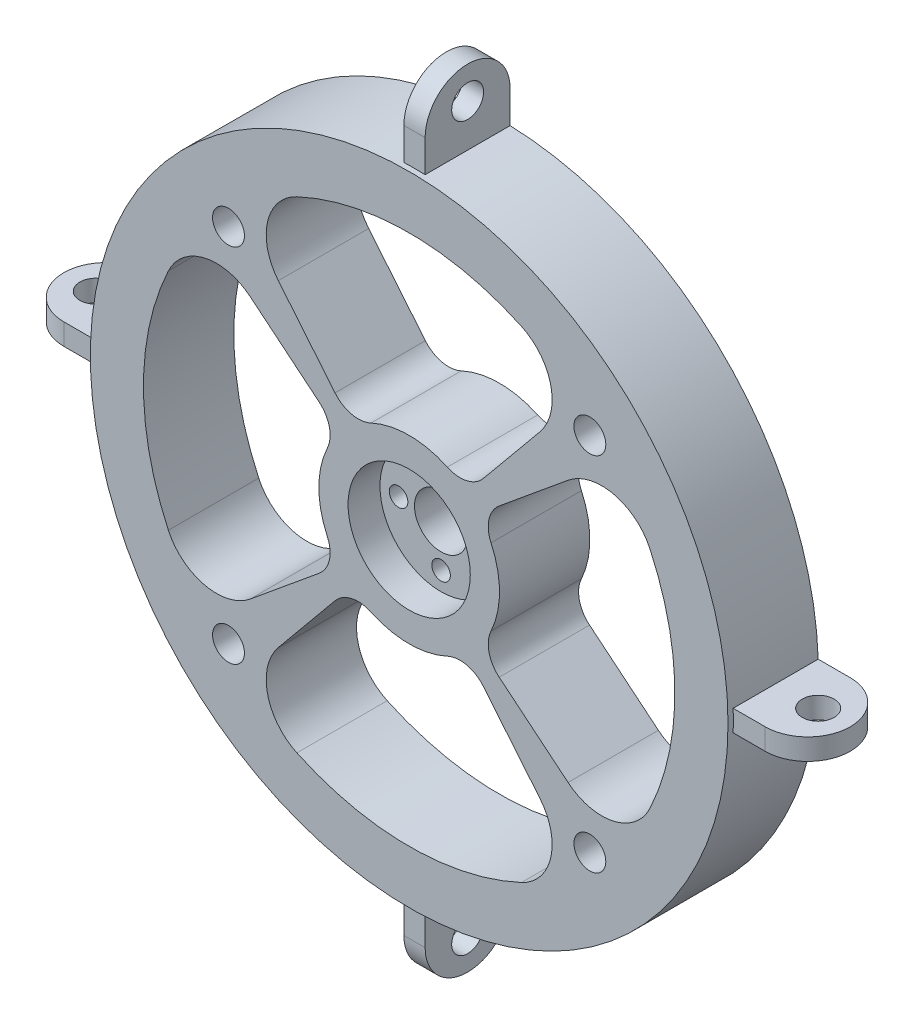
SolidWorks part; units mm, degrees
material "ABS"
ref_plane "前视基准面" through (0, 0, 0) normal (0, 0, 1) x (1, 0, 0)
ref_plane "上视基准面" through (0, 0, 0) normal (0, 1, 0) x (1, 0, 0)
ref_plane "右视基准面" through (0, 0, 0) normal (1, 0, 0) x (0, 0, -1)
sketch "草图1" plane through (0, 0, 0) normal (0, 0, 1) x (1, 0, 0)
  circle A0 centre (0, 0) radius 60
  dimension "D1" = 120
extrude "凸台-拉伸1" add sketch "草图1" along normal blind 17
sketch "草图2" plane through (0, 0, 17) normal (0, 0, 1) x (1, 0, 0)
  line L0 (0, 30) -> (0, 0) construction
  line L1 (0, 0) -> (0, -30) construction
  line L2 (-30, 0) -> (0, 0) construction
  line L3 (0, 0) -> (30, 0) construction
  circle A4 centre (-34, 34) radius 3
  circle A5 centre (34, 34) radius 3
  circle A6 centre (34, -34) radius 3
  circle A7 centre (-34, -34) radius 3
  dimension "D1" = 6
  dimension "D2" = 6
  dimension "D7" = 6
  dimension "D8" = 6
  dimension "D3" = 30
  dimension "D4" = 30
  dimension "D5" = 30
  dimension "D6" = 30
  dimension "D9" = 68
  dimension "D10" = 68
extrude "切除-拉伸1" cut sketch "草图2" against normal through all
sketch "草图3" plane through (0, 0, 0) normal (1, 0, 0) x (0, 0, -1)
  line L0 (0, 58) -> (-16, 58)
  line L1 (-16, 58) -> (-16, 66)
  line L2 (0, 66) -> (0, 58)
  line L3 (0, 0) -> (-35.6052, 0) construction
  arc A0 (-16, 66) -> (0, 66) centre (-8, 66) cw
  dimension "D3" = 8
  dimension "D1" = 58
  dimension "D2" = 8
  dimension "D4" = 0
extrude "凸台-拉伸2" add sketch "草图3" along normal blind 2 and the other way blind 2
sketch "草图4" plane through (2, 0, 0) normal (1, 0, 0) x (0, 0, -1)
  line L0 (-16, 59.9667) -> (0, 59.9667) construction
  line L1 (0, 59.9667) -> (0, 66) construction
  circle A0 centre (-8, 67.9667) radius 3
  dimension "D1" = 6
  dimension "D2" = 8
  dimension "D3" = 8
extrude "切除-拉伸7" cut sketch "草图4" against normal through all
sketch "草图5" plane through (0, 0, 0) normal (0, 0, -1) x (-1, 0, 0)
  circle A0 centre (0, 0) radius 5
  dimension "D1" = 10
extrude "切除-拉伸3" cut sketch "草图5" against normal up to next
sketch "草图6" plane through (0, 0, 17) normal (0, 0, 1) x (1, 0, 0)
  circle A0 centre (0, 0) radius 11.5
  dimension "D1" = 23
extrude "切除-拉伸4" cut sketch "草图6" against normal blind 6
sketch "草图7" plane through (0, 0, 11) normal (0, 0, 1) x (1, 0, 0)
  circle A0 centre (0, 0) radius 8 construction
  circle A1 centre (-8, 0) radius 1.75
  circle A2 centre (0, 8) radius 1.75
  circle A3 centre (8, 0) radius 1.75
  circle A4 centre (0, -8) radius 1.75
  dimension "D1" = 16
  dimension "D2" = 3.5
  dimension "D3" = 3.5
  dimension "D4" = 3.5
  dimension "D5" = 3.5
extrude "切除-拉伸5" cut sketch "草图7" against normal up to next
sketch "草图8" plane through (0, 0, 17) normal (0, 0, 1) x (1, 0, 0)
  line L0 (-36.2523, -16.9047) -> (0, 0) construction
  line L1 (0, 0) -> (-36.2523, 16.9047) construction
  line L2 (0, 0) -> (-30, 0) construction
  line L3 (-36.2523, -16.9047) -> (-45.3154, -21.1309) construction
  line L4 (-36.2523, 16.9047) -> (-45.3154, 21.1309) construction
  line L13 (-16.9402, -13.9533) -> (0, 0) construction
  line L14 (-16.9402, 13.9533) -> (-29.8946, 24.6235)
  line L15 (-29.8946, -24.6235) -> (-16.9402, -13.9533)
  arc A0 (-36.2523, -16.9047) -> (-36.2523, 16.9047) centre (0, 0) cw construction
  arc A6 (-45.3154, -21.1309) -> (-45.3154, 21.1309) centre (0, 0) cw
  arc A7 (-45.3154, -21.1309) -> (-29.8946, -24.6235) centre (-36.2523, -16.9047) ccw
  arc A9 (-15.4072, -7.1845) -> (-15.4072, 7.1845) centre (0, 0) cw
  arc A11 (-15.4072, -7.1845) -> (-16.9402, -13.9533) centre (-20.543, -9.5793) cw
  arc A31 (-15.4072, 7.1845) -> (-16.9402, 13.9533) centre (-20.543, 9.5793) ccw
  arc A32 (-45.3154, 21.1309) -> (-29.8946, 24.6235) centre (-36.2523, 16.9047) cw
  dimension "D2" = 25
  dimension "D3" = 40
  dimension "D4" = 50
  dimension "D5" = 17
extrude "切除-拉伸6" cut sketch "草图8" against normal up to next
pattern_circular "阵列(圆周)3" count 4 over 360 about axis through (0, 0, 17) along (0, 0, 1) of "切除-拉伸6"
pattern_circular "阵列(圆周)4" count 4 over 360 about axis through (0, 0, 17) along (0, 0, 1) of "凸台-拉伸2", "切除-拉伸7"
